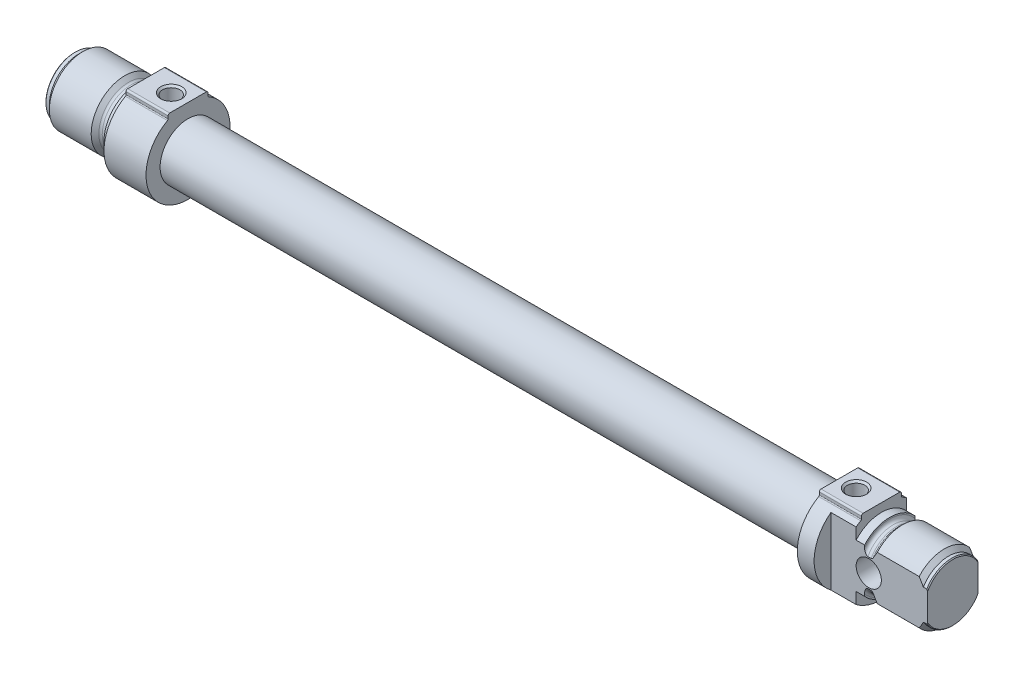
SolidWorks part; units mm, degrees
ref_plane "Ebene vorne" through (0, 0, 0) normal (0, 0, 1) x (1, 0, 0)
ref_plane "Ebene oben" through (0, 0, 0) normal (0, 1, 0) x (1, 0, 0)
ref_plane "Ebene rechts" through (0, 0, 0) normal (1, 0, 0) x (0, 0, -1)
sketch "Skizze1" plane through (0, 0, 0) normal (0, 0, 1) x (1, 0, 0)
  line L0 (0, 0) -> (0, 6.8)
  line L1 (0, 6.8) -> (0.2, 7)
  line L2 (0.2, 7) -> (1, 7)
  line L3 (1, 7) -> (2, 8)
  line L4 (2, 8) -> (11.95, 8)
  line L5 (11.95, 8) -> (12.8657, 7.0843)
  line L6 (13.4314, 6.85) -> (14.2, 6.85)
  line L7 (15, 7.65) -> (15, 8)
  line L8 (15, 8) -> (17, 8)
  line L9 (17, 8) -> (17, 0)
  line L10 (17, 0) -> (0, 0)
  line L11 (17, 0) -> (0, 0) construction
  arc A0 (12.8657, 7.0843) -> (13.4314, 6.85) centre (13.4314, 7.65) ccw
  arc A1 (14.2, 6.85) -> (15, 7.65) centre (14.2, 7.65) ccw
revolve "Rotation1" add sketch "Skizze1" angle 360 about L11 reverse direction yes
cosmetic thread "Gewindedarstellung1" parameters "D1"=10.87, "D2"=14.16
ref_plane "Ebene1" through (21.1, 0, 0) normal (1, 0, 0) x (0, 0, -1)
ref_plane "Ebene2" through (9, 0, 0) normal (1, 0, 0) x (0, 0, -1)
ref_plane "Ebene3" through (0, -11, 0) normal (0, 1, 0) x (1, 0, 0)
ref_plane "Ebene4" through (0, 11, 0) normal (0, 1, 0) x (1, 0, 0)
ref_plane "Ebene5" through (0, 0, 0) normal (0, 1, 0) x (1, 0, 0)
ref_plane "Ebene6" through (0, 0, 0) normal (0, 1, 0) x (1, 0, 0)
ref_plane "Ebene7" through (17, 0, 0) normal (1, 0, 0) x (0, 0, -1)
ref_plane "Ebene8" through (17, 0, 0) normal (1, 0, 0) x (0, 0, -1)
ref_plane "Ebene9" through (27, 0, 0) normal (1, 0, 0) x (0, 0, -1)
ref_plane "Ebene10" through (17, 0, 0) normal (1, 0, 0) x (0, 0, -1)
ref_plane "Ebene11" through (17, 0, 0) normal (1, 0, 0) x (0, 0, -1)
sketch "Skizze2" plane through (17, 0, 0) normal (1, 0, 0) x (0, 0, -1)
  line L0 (4.75, 8.9771) -> (4.75, 9.6)
  line L1 (4.35, 10) -> (-4.35, 10)
  line L2 (-4.75, 9.6) -> (-4.75, 8.9771)
  arc A0 (-4.9029, 8.7156) -> (4.9029, 8.7156) centre (0, 0) ccw
  arc A1 (4.9029, 8.7156) -> (4.75, 8.9771) centre (5.05, 8.9771) cw
  arc A2 (4.75, 9.6) -> (4.35, 10) centre (4.35, 9.6) ccw
  arc A3 (-4.35, 10) -> (-4.75, 9.6) centre (-4.35, 9.6) ccw
  arc A4 (-4.75, 8.9771) -> (-4.9029, 8.7156) centre (-5.05, 8.9771) cw
extrude "Aufsatz-Linear austragen1" add sketch "Skizze2" along normal blind 10
ref_plane "Ebene12" through (23, 0, 0) normal (1, 0, 0) x (0, 0, -1)
ref_plane "Ebene13" through (0, 0, 0) normal (0, 0, 1) x (1, 0, 0)
ref_plane "Ebene14" through (0, 0, -5.7) normal (0, 0, 1) x (1, 0, 0)
ref_plane "Ebene15" through (0, 0, 0) normal (0, 1, 0) x (1, 0, 0)
ref_plane "Ebene16" through (0, 7.5, 0) normal (0, 1, 0) x (1, 0, 0)
ref_plane "Ebene17" through (0, 0, -6.6) normal (0, 0, 1) x (1, 0, 0)
ref_plane "Ebene18" through (0, 0, 0) normal (0, 1, 0) x (1, 0, 0)
ref_plane "Ebene19" through (0, 7.5, 0) normal (0, 1, 0) x (1, 0, 0)
ref_plane "Ebene20" through (0, 8.4025, -1.4816) normal (0, 0.9848, -0.1736) x (1, 0, 0)
ref_plane "Ebene21" through (0, 6.9253, -1.2211) normal (0, 0.9848, -0.1736) x (1, 0, 0)
sketch "Skizze3" plane through (0, 0, 0) normal (0, 0, 1) x (1, 0, 0)
  line L0 (27, 0) -> (27, 6.65)
  line L1 (27, 6.65) -> (182, 6.65)
  line L2 (182, 6.65) -> (182, 0)
  line L3 (182, 0) -> (27, 0)
  line L4 (182, 0) -> (27, 0) construction
revolve "Rotation2" add sketch "Skizze3" angle 360 about L4 reverse direction yes
ref_plane "Ebene22" through (182, 0, 0) normal (1, 0, 0) x (0, 0, -1)
sketch "Skizze4" plane through (182, 0, 0) normal (1, 0, 0) x (0, 0, -1)
  line L0 (4.75, 8.9771) -> (4.75, 9.6)
  line L1 (4.35, 10) -> (-4.35, 10)
  line L2 (-4.75, 9.6) -> (-4.75, 8.9771)
  arc A0 (-4.9029, 8.7156) -> (4.9029, 8.7156) centre (0, 0) ccw
  arc A1 (4.9029, 8.7156) -> (4.75, 8.9771) centre (5.05, 8.9771) cw
  arc A2 (4.75, 9.6) -> (4.35, 10) centre (4.35, 9.6) ccw
  arc A3 (-4.35, 10) -> (-4.75, 9.6) centre (-4.35, 9.6) ccw
  arc A4 (-4.75, 8.9771) -> (-4.9029, 8.7156) centre (-5.05, 8.9771) cw
extrude "Aufsatz-Linear austragen2" add sketch "Skizze4" along normal blind 10
ref_plane "Ebene23" through (183.85, 0, 0) normal (1, 0, 0) x (0, 0, -1)
ref_plane "Ebene24" through (186, 0, 0) normal (1, 0, 0) x (0, 0, -1)
ref_plane "Ebene25" through (0, 0, 6.6) normal (0, 0, 1) x (1, 0, 0)
ref_plane "Ebene26" through (0, 0, 0) normal (0, 1, 0) x (1, 0, 0)
ref_plane "Ebene27" through (0, 7.5, 0) normal (0, 1, 0) x (1, 0, 0)
ref_plane "Ebene28" through (0, 8.4025, 1.4816) normal (0, 0.9848, 0.1736) x (1, 0, 0)
ref_plane "Ebene29" through (0, 6.9253, 1.2211) normal (0, 0.9848, 0.1736) x (1, 0, 0)
ref_plane "Ebene30" through (230, 0, 0) normal (1, 0, 0) x (0, 0, -1)
sketch "Skizze5" plane through (0, 0, 0) normal (0, 0, 1) x (1, 0, 0)
  line L0 (192, 0) -> (192, 8)
  line L1 (192, 8) -> (194, 8)
  line L2 (194, 8) -> (194, 7.65)
  line L3 (194.8, 6.85) -> (195.5686, 6.85)
  line L4 (196.1343, 7.0843) -> (197.05, 8)
  line L5 (197.05, 8) -> (207, 8)
  line L6 (207, 8) -> (208, 7)
  line L7 (208, 7) -> (208.8, 7)
  line L8 (208.8, 7) -> (209, 6.8)
  line L9 (209, 6.8) -> (209, 0)
  line L10 (209, 0) -> (192, 0)
  line L11 (209, 0) -> (192, 0) construction
  arc A0 (194, 7.65) -> (194.8, 6.85) centre (194.8, 7.65) ccw
  arc A1 (195.5686, 6.85) -> (196.1343, 7.0843) centre (195.5686, 7.65) ccw
revolve "Rotation3" add sketch "Skizze5" angle 360 about L11 reverse direction yes
cosmetic thread "Gewindedarstellung2" parameters "D1"=9.87, "D2"=14.16
ref_plane "Ebene31" through (220, 0, 0) normal (1, 0, 0) x (0, 0, -1)
ref_plane "Ebene32" through (230, 0, 0) normal (1, 0, 0) x (0, 0, -1)
ref_plane "Ebene33" through (230, 0, 0) normal (1, 0, 0) x (0, 0, -1)
sketch "Skizze6" plane through (0, 0, 0) normal (0, 1, 0) x (1, 0, 0)
  line L0 (186, 18) -> (186, 6)
  line L1 (186, 6) -> (209, 6)
  line L2 (209, 6) -> (209, -6)
  line L3 (209, -6) -> (186, -6)
  line L4 (186, -6) -> (186, -18)
  line L5 (186, -18) -> (221, -18)
  line L6 (221, -18) -> (221, 18)
  line L7 (221, 18) -> (186, 18)
extrude "Schnitt-Linear austragen1" cut sketch "Skizze6" along normal blind 10 and the other way blind 10
ref_plane "Ebene34" through (195, 0, 0) normal (1, 0, 0) x (0, 0, -1)
hole_wizard "Bohrung1" positions "Skizze8" profile "Skizze7" legacy
sketch "Skizze8" plane through (0, 0, -6) normal (0, 0, -1) x (-1, 0, 0)
  point P0 (-195, 0)
sketch "Skizze7" plane through (195, 0, -6) normal (1, 0, 0) x (0, 1, 0)
  line L0 (0, 0) -> (0, 12)
  line L1 (0, 12) -> (3, 12)
  line L2 (3, 12) -> (3, 0)
  line L3 (3, 0) -> (0, 0)
  line L4 (0, 110) -> (0, -10) construction
  dimension "Durchmesser" = 6
  dimension "Tiefe" = 12
hole_wizard "Bohrung2" positions "Skizze10" profile "Skizze9" legacy
sketch "Skizze10" plane through (0, 10, 0) normal (0, 1, 0) x (1, 0, 0)
  point P0 (23, 0)
sketch "Skizze9" plane through (23, 10, 0) normal (1, 0, 0) x (0, 0, 1)
  line L0 (0, 0) -> (0, 10)
  line L1 (0, 10) -> (2.067, 10)
  line L2 (2.067, 10) -> (2.067, 0.433)
  line L3 (2.067, 0.433) -> (2.5, 0)
  line L4 (2.5, 0) -> (0, 0)
  line L5 (0, -6.4453) -> (0, 115.525) construction
  line L6 (-2.067, 0.433) -> (-2.5, 0) construction
  dimension "Durchmesser" = 4.134
  dimension "Tiefe" = 10
  dimension "Senkwinkel1" = 90
  dimension "Senkdurchmesser3" = 5
cosmetic thread "Gewindedarstellung3" parameters "D1"=7, "D2"=5
hole_wizard "Bohrung3" positions "Skizze12" profile "Skizze11" legacy
sketch "Skizze12" plane through (0, 10, 0) normal (0, 1, 0) x (1, 0, 0)
  point P0 (186, 0)
sketch "Skizze11" plane through (186, 10, 0) normal (1, 0, 0) x (0, 0, 1)
  line L0 (0, 0) -> (0, 12.1934)
  line L1 (0, 12.1934) -> (2.067, 11)
  line L2 (2.067, 11) -> (2.067, 0.433)
  line L3 (2.067, 0.433) -> (2.5, 0)
  line L4 (2.5, 0) -> (0, 0)
  line L5 (0, -14.3089) -> (0, 102.4216) construction
  line L6 (0, 12.1934) -> (-2.067, 11) construction
  line L7 (-2.067, 0.433) -> (-2.5, 0) construction
  dimension "Durchmesser" = 4.134
  dimension "Tiefe" = 11
  dimension "Senkdurchmesser1" = 5
  dimension "Senkwinkel1" = 90
  dimension "Spitzenwinkel" = 120
cosmetic thread "Gewindedarstellung4" parameters "D1"=6, "D2"=5
sketch "Skizze13" plane through (0, 0, 0) normal (0, 0, 1) x (1, 0, 0)
  line L0 (-5, 0) -> (-5, 3)
  line L1 (-5, 3) -> (37.3, 3)
  line L2 (37.3, 3) -> (37.3, 6)
  line L3 (37.3, 6) -> (165.3, 6)
  line L4 (165.3, 6) -> (165.3, 0)
  line L5 (165.3, 0) -> (-5, 0)
  line L6 (165.3, 0) -> (-5, 0) construction
revolve "Schnitt-Rotation1" cut sketch "Skizze13" angle 360 about L6 reverse direction yes
ref_plane "Ebene35" through (-5, 0, 0) normal (1, 0, 0) x (0, 0, -1)
ref_plane "Ebene36" through (0, 10, 0) normal (0, 1, 0) x (1, 0, 0)
ref_plane "Ebene37" through (8, 0, 0) normal (1, 0, 0) x (0, 0, -1)
ref_plane "Ebene38" through (0, 0, 0) normal (1, 0, 0) x (0, 0, -1)
ref_plane "Ebene39" through (17, 0, 0) normal (1, 0, 0) x (0, 0, -1)
ref_plane "Ebene40" through (192, 0, 0) normal (1, 0, 0) x (0, 0, -1)
ref_plane "Ebene41" through (17, 0, 0) normal (1, 0, 0) x (0, 0, -1)
ref_plane "Ebene42" through (0, 10, 0) normal (0, 1, 0) x (1, 0, 0)
ref_plane "Ebene43" through (36.5, 0, 0) normal (1, 0, 0) x (0, 0, -1)
ref_plane "Ebene44" through (172.5, 0, 0) normal (1, 0, 0) x (0, 0, -1)
ref_plane "Ebene45" through (0, 0, 0) normal (0, 0, 1) x (1, 0, 0)
ref_plane "Ebene46" through (17, 0, 0) normal (1, 0, 0) x (0, 0, -1)
ref_plane "Ebene47" through (0, 10, 0) normal (0, 1, 0) x (1, 0, 0)
ref_plane "FDT_FRONT XY" through (17, 0, 0) normal (1, 0, 0) x (0, 0, -1)
ref_plane "FDT_FRONT XZ" through (0, 0, 0) normal (0, -1, 0) x (-1, 0, 0)
ref_plane "FDT_FRONT YZ" through (0, 0, 0) normal (0, 0, -1) x (-1, 0, 0)
ref_axis "FDT_FRONT X" through (17, 0, 80.9) along (0, 0, -1)
ref_axis "FDT_FRONT Y" through (17, -50, 0) along (0, 1, 0)
ref_axis "FDT_FRONT Z" through (80.9, 0, 0) along (-1, 0, 0)
sketch3d "FDT_FRONT"
  point P0 (17, 0, 0)
ref_plane "FDT_QSFRONT XY" through (0, 10, 0) normal (0, 1, 0) x (1, 0, 0)
ref_plane "FDT_QSFRONT XZ" through (23, 0, 0) normal (-1, 0, 0) x (0, 0, 1)
ref_plane "FDT_QSFRONT YZ" through (0, 0, 0) normal (0, 0, 1) x (1, 0, 0)
ref_axis "FDT_QSFRONT X" through (23, 10, -50) along (0, 0, 1)
ref_axis "FDT_QSFRONT Y" through (-80.9, 10, 0) along (1, 0, 0)
ref_axis "FDT_QSFRONT Z" through (23, 50, 0) along (0, -1, 0)
sketch3d "FDT_QSFRONT"
  point P0 (23, 10, 0)
ref_plane "FDT_QSREAR XY" through (0, 10, 0) normal (0, 1, 0) x (1, 0, 0)
ref_plane "FDT_QSREAR XZ" through (186, 0, 0) normal (-1, 0, 0) x (0, 0, 1)
ref_plane "FDT_QSREAR YZ" through (0, 0, 0) normal (0, 0, 1) x (1, 0, 0)
ref_axis "FDT_QSREAR X" through (186, 10, -50) along (0, 0, 1)
ref_axis "FDT_QSREAR Y" through (-80.9, 10, 0) along (1, 0, 0)
ref_axis "FDT_QSREAR Z" through (186, 50, 0) along (0, -1, 0)
sketch3d "FDT_QSREAR"
  point P0 (186, 10, 0)
ref_plane "FDT_REAR XY" through (192, 0, 0) normal (-1, 0, 0) x (0, 0, 1)
ref_plane "FDT_REAR XZ" through (0, 0, 0) normal (0, 1, 0) x (1, 0, 0)
ref_plane "FDT_REAR YZ" through (0, 0, 0) normal (0, 0, -1) x (-1, 0, 0)
ref_axis "FDT_REAR X" through (192, 0, 80.9) along (0, 0, -1)
ref_axis "FDT_REAR Y" through (192, 50, 0) along (0, -1, 0)
ref_axis "FDT_REAR Z" through (-80.9, 0, 0) along (1, 0, 0)
sketch3d "FDT_REAR"
  point P0 (192, 0, 0)
ref_plane "FDT_SMBR1 XY" through (36.5, 0, 0) normal (-1, 0, 0) x (0, 0, 1)
ref_plane "FDT_SMBR1 XZ" through (0, 0, 0) normal (0, -1, 0) x (-1, 0, 0)
ref_plane "FDT_SMBR1 YZ" through (0, 0, 0) normal (0, 0, 1) x (1, 0, 0)
ref_axis "FDT_SMBR1 X" through (36.5, 0, -80.9) along (0, 0, 1)
ref_axis "FDT_SMBR1 Y" through (36.5, -50, 0) along (0, 1, 0)
ref_axis "FDT_SMBR1 Z" through (-80.9, 0, 0) along (1, 0, 0)
sketch3d "FDT_SMBR1"
  point P0 (36.5, 0, 0)
ref_plane "FDT_SMBR2 XY" through (172.5, 0, 0) normal (-1, 0, 0) x (0, 0, 1)
ref_plane "FDT_SMBR2 XZ" through (0, 0, 0) normal (0, -1, 0) x (-1, 0, 0)
ref_plane "FDT_SMBR2 YZ" through (0, 0, 0) normal (0, 0, 1) x (1, 0, 0)
ref_axis "FDT_SMBR2 X" through (172.5, 0, -80.9) along (0, 0, 1)
ref_axis "FDT_SMBR2 Y" through (172.5, -50, 0) along (0, 1, 0)
ref_axis "FDT_SMBR2 Z" through (-80.9, 0, 0) along (1, 0, 0)
sketch3d "FDT_SMBR2"
  point P0 (172.5, 0, 0)
ref_plane "FDT_SWIVELAXIS XY" through (0, 0, 0) normal (0, 0, 1) x (1, 0, 0)
ref_plane "FDT_SWIVELAXIS XZ" through (0, 0, 0) normal (0, -1, 0) x (-1, 0, 0)
ref_plane "FDT_SWIVELAXIS YZ" through (195, 0, 0) normal (1, 0, 0) x (0, 0, -1)
ref_axis "FDT_SWIVELAXIS X" through (-80.9, 0, 0) along (1, 0, 0)
ref_axis "FDT_SWIVELAXIS Y" through (195, -50, 0) along (0, 1, 0)
ref_axis "FDT_SWIVELAXIS Z" through (195, 0, 80.9) along (0, 0, -1)
sketch3d "FDT_SWIVELAXIS"
  point P0 (195, 0, 0)
ref_plane "NUT XY" through (8, 0, 0) normal (1, 0, 0) x (0, 0, -1)
ref_plane "NUT XZ" through (0, 0, 0) normal (0, -1, 0) x (-1, 0, 0)
ref_plane "NUT YZ" through (0, 0, 0) normal (0, 0, -1) x (-1, 0, 0)
ref_axis "NUT X" through (8, 0, 80.9) along (0, 0, -1)
ref_axis "NUT Y" through (8, -50, 0) along (0, 1, 0)
ref_axis "NUT Z" through (80.9, 0, 0) along (-1, 0, 0)
sketch3d "NUT"
  point P0 (8, 0, 0)
ref_plane "ZR XY" through (0, 0, 0) normal (1, 0, 0) x (0, 0, -1)
ref_plane "ZR XZ" through (0, 0, 0) normal (0, -1, 0) x (-1, 0, 0)
ref_plane "ZR YZ" through (0, 0, 0) normal (0, 0, -1) x (-1, 0, 0)
ref_axis "ZR X" through (0, 0, 80.9) along (0, 0, -1)
ref_axis "ZR Y" through (0, -50, 0) along (0, 1, 0)
ref_axis "ZR Z" through (80.9, 0, 0) along (-1, 0, 0)
sketch3d "ZR"
  point P0 (0, 0, 0)
ref_plane "ZYL XY" through (17, 0, 0) normal (1, 0, 0) x (0, 0, -1)
ref_plane "ZYL XZ" through (0, 0, 0) normal (0, -1, 0) x (-1, 0, 0)
ref_plane "ZYL YZ" through (0, 0, 0) normal (0, 0, -1) x (-1, 0, 0)
ref_axis "ZYL X" through (17, 0, 80.9) along (0, 0, -1)
ref_axis "ZYL Y" through (17, -50, 0) along (0, 1, 0)
ref_axis "ZYL Z" through (80.9, 0, 0) along (-1, 0, 0)
sketch3d "ZYL"
  point P0 (17, 0, 0)
